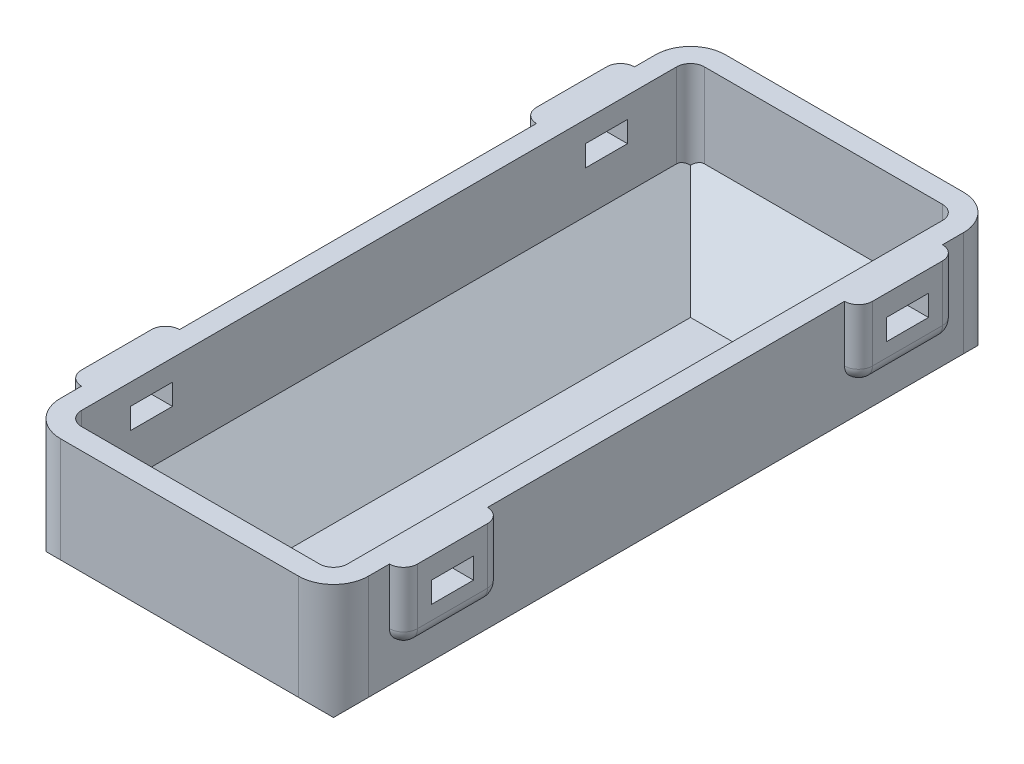
SolidWorks part; units mm, degrees
ref_plane "Front Plane" through (0, 0, 0) normal (0, 0, 1) x (1, 0, 0)
ref_plane "Top Plane" through (0, 0, 0) normal (0, 1, 0) x (1, 0, 0)
ref_plane "Right Plane" through (0, 0, 0) normal (1, 0, 0) x (0, 0, -1)
sketch "Sketch1" plane through (0, 0, 0) normal (0, 1, 0) x (1, 0, 0)
  line L1 (-22, -47.5) -> (22, -47.5)
  line L2 (-22, -47.5) -> (-22, 47.5)
  line L3 (-22, 47.5) -> (22, 47.5)
  line L4 (22, -47.5) -> (22, 47.5)
  line L5 (-22, -47.5) -> (22, 47.5) construction
  line L6 (-22, 47.5) -> (22, -47.5) construction
  point P0 (0, 0)
  dimension "D1" = 95
  dimension "D2" = 44
extrude "Boss-Extrude1" add sketch "Sketch1" along normal blind 25
sketch "Sketch2" plane through (0, 25, 0) normal (0, 1, 0) x (1, 0, 0)
  line L1 (19, -44.5) -> (-19, -44.5)
  line L2 (19, -44.5) -> (19, 44.5)
  line L3 (19, 44.5) -> (-19, 44.5)
  line L4 (-19, -44.5) -> (-19, 44.5)
  line L5 (19, -44.5) -> (-19, 44.5) construction
  line L6 (19, 44.5) -> (-19, -44.5) construction
  point P0 (0, 0)
  dimension "D1" = 89
  dimension "D2" = 38
extrude "Cut-Extrude1" cut sketch "Sketch2" against normal blind 22
chamfer "Chamfer1" distance 10 angle 45 8 edges at (0, 0, -47.5) (-22, 0, 0) (0, 0, 47.5) (22, 0, 0) (0, 3, -44.5) (19, 3, 0) (0, 3, 44.5) (-19, 3, 0)
fillet "Fillet1" radius 2 4 edges at (-19, 19, 44.5) (19, 19, 44.5) (19, 19, -44.5) (-19, 19, -44.5)
fillet "Fillet2" radius 5 4 edges at (22, 17.5, -47.5) (22, 17.5, 47.5) (-22, 17.5, 47.5) (-22, 17.5, -47.5)
sketch "Sketch3" plane through (22, 0, 0) normal (1, 0, 0) x (0, 0, -1)
  line L0 (-42.5, 25) -> (42.5, 25) construction
  line L1 (-25.5, 15) -> (-39.5, 15)
  line L2 (-25.5, 15) -> (-25.5, 25)
  line L3 (-25.5, 25) -> (-39.5, 25)
  line L4 (-39.5, 15) -> (-39.5, 25)
  line L5 (-25.5, 15) -> (-39.5, 25) construction
  line L6 (-25.5, 25) -> (-39.5, 15) construction
  line L7 (-42.5, 25) -> (-42.5, 10) construction
  line L8 (0, 25) -> (0, 10) construction
  line L9 (-29.5, 17.8571) -> (-35.5, 17.8571) construction
  line L10 (-29.5, 17.8571) -> (-29.5, 22.1429) construction
  line L11 (-29.5, 22.1429) -> (-35.5, 22.1429) construction
  line L12 (-35.5, 17.8571) -> (-35.5, 22.1429) construction
  line L13 (-29.5, 17.8571) -> (-35.5, 22.1429) construction
  line L14 (-29.5, 22.1429) -> (-35.5, 17.8571) construction
  line L15 (-42.5, 10) -> (42.5, 10) construction
  line L16 (25.5, 25) -> (39.5, 25)
  line L17 (29.5, 22.1429) -> (35.5, 17.8571) construction
  line L18 (29.5, 17.8571) -> (35.5, 22.1429) construction
  line L19 (35.5, 17.8571) -> (35.5, 22.1429) construction
  line L20 (29.5, 22.1429) -> (35.5, 22.1429) construction
  line L21 (29.5, 17.8571) -> (29.5, 22.1429) construction
  line L22 (29.5, 17.8571) -> (35.5, 17.8571) construction
  line L23 (25.5, 25) -> (39.5, 15) construction
  line L24 (25.5, 15) -> (39.5, 25) construction
  line L25 (39.5, 15) -> (39.5, 25)
  line L26 (25.5, 15) -> (25.5, 25)
  line L27 (25.5, 15) -> (39.5, 15)
  point P0 (-32.5, 20)
  point P9 (-32.5, 20)
  point P26 (32.5, 20)
  dimension "D1" = 3
  dimension "D2" = 14
  dimension "D3" = 10
  dimension "D4" = 6
extrude "Boss-Extrude2" add sketch "Sketch3" along normal blind 2
sketch "Sketch5" plane through (-22, 0, 0) normal (-1, 0, 0) x (0, 0, 1)
  line L0 (-42.5, 25) -> (42.5, 25) construction
  line L1 (25.5, 15) -> (39.5, 15)
  line L2 (25.5, 15) -> (25.5, 25)
  line L3 (25.5, 25) -> (39.5, 25)
  line L4 (39.5, 15) -> (39.5, 25)
  line L5 (25.5, 15) -> (39.5, 25) construction
  line L6 (25.5, 25) -> (39.5, 15) construction
  line L7 (42.5, 10) -> (42.5, 25) construction
  line L8 (0, 25) -> (0, 10) construction
  line L9 (-42.5, 10) -> (42.5, 10) construction
  line L10 (-39.5, 15) -> (-39.5, 25)
  line L11 (-25.5, 25) -> (-39.5, 15) construction
  line L12 (-25.5, 15) -> (-39.5, 25) construction
  line L13 (-25.5, 25) -> (-39.5, 25)
  line L14 (-25.5, 15) -> (-25.5, 25)
  line L15 (-25.5, 15) -> (-39.5, 15)
  point P0 (32.5, 20)
  point P17 (-32.5, 20)
  dimension "D1" = 10
  dimension "D2" = 14
  dimension "D3" = 3
extrude "Boss-Extrude3" add sketch "Sketch5" along normal blind 2
sketch "Sketch4" plane through (24, 0, 0) normal (1, 0, 0) x (0, 0, -1)
  line L0 (-25.5, 25) -> (-39.5, 25) construction
  line L1 (-29.5, 19) -> (-35.5, 19)
  line L2 (-29.5, 19) -> (-29.5, 22)
  line L3 (-29.5, 22) -> (-35.5, 22)
  line L4 (-35.5, 19) -> (-35.5, 22)
  line L5 (-29.5, 19) -> (-35.5, 22) construction
  line L6 (-29.5, 22) -> (-35.5, 19) construction
  line L7 (-25.5, 15) -> (-25.5, 25) construction
  line L8 (0, 25) -> (0, 10) construction
  line L9 (29.5, 22) -> (35.5, 19) construction
  line L10 (29.5, 19) -> (35.5, 22) construction
  line L11 (35.5, 19) -> (35.5, 22)
  line L12 (29.5, 22) -> (35.5, 22)
  line L13 (29.5, 19) -> (29.5, 22)
  line L14 (29.5, 19) -> (35.5, 19)
  point P0 (-32.5, 20.5)
  point P17 (32.5, 20.5)
  dimension "D1" = 3
  dimension "D2" = 3
  dimension "D3" = 6
  dimension "D4" = 4
extrude "Cut-Extrude2" cut sketch "Sketch4" against normal through all both and the other way through all
fillet "Fillet3" radius 2 12 edges at (24, 20, 25.5) (24, 15, 32.5) (24, 20, 39.5) (24, 20, -25.5) (24, 15, -32.5) (24, 20, -39.5) (-24, 20, 39.5) (-24, 15, 32.5) (-24, 20, 25.5) (-24, 20, -25.5) (-24, 15, -32.5) (-24, 20, -39.5)
